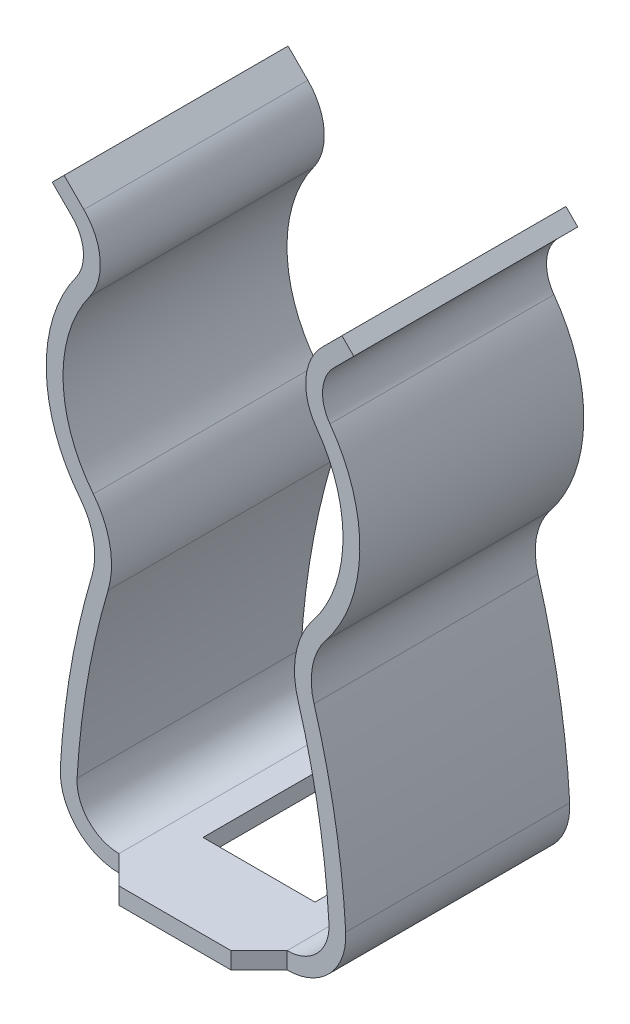
SolidWorks part; units mm, degrees
material "Медь"
ref_plane "Спереди" through (0, 0, 0) normal (0, 0, 1) x (1, 0, 0)
ref_plane "Сверху" through (0, 0, 0) normal (0, 1, 0) x (1, 0, 0)
ref_plane "Справа" through (0, 0, 0) normal (1, 0, 0) x (0, 0, -1)
sketch "Эскиз1" plane through (0, 0, 0) normal (0, 0, 1) x (1, 0, 0)
  line L0 (11.7288, 0) -> (0, 0) construction
  line L2 (0, 12.9831) -> (0, 6.8861) construction
  line L6 (-3.1336, 4.4) -> (3.1336, 4.4) construction
  line L7 (0, 4.4) -> (0, 6.8861) construction
  line L9 (-1.5, 0) -> (0, 0)
  line L10 (0, 0) -> (0, 4.4) construction
  line L13 (-2.1273, 9.6464) -> (-2.4809, 10)
  arc A0 (-2.0246, 8.3527) -> (-1.9585, 5.3323) centre (0, 6.8861) ccw
  arc A2 (-2.0246, 8.3527) -> (-2.1273, 9.6464) centre (-2.8344, 8.9393) ccw
  arc A3 (-1.6953, 3.9742) -> (-1.9585, 5.3323) centre (-3.1336, 4.4) ccw
  arc A6 (-1.6953, 3.9742) -> (-2.2488, 0.7925) centre (11.7288, 0) ccw
  arc A7 (-1.5, 0) -> (-2.2488, 0.7925) centre (-1.5, 0.75) cw
  circle A20 centre (0, 6.8861) radius 2.5 construction
  point P1 (0, 0)
  dimension "D6" = 0.75
  dimension "D8" = 10
  dimension "D9" = 4.4
  dimension "D10" = 5
  dimension "D2" = 2.5
  dimension "D3" = 1
  dimension "D4" = 14
  dimension "D7" = 1.5
  dimension "D5" = 1.5
  dimension "D11" = 45
  dimension "D12" = 0.5
extrude "Вытянуть-Тонкостенный1" add sketch "Эскиз1" along normal mid plane 4 thin thin type one direction reverse wall 0.3
mirror "Зеркальное отражение1" about plane through (0, 0, 0) normal (1, 0, 0) of "Вытянуть-Тонкостенный1"
sketch "Эскиз2" plane through (0, -0.3, 0) normal (0, -1, 0) x (1, 0, 0)
  line L0 (-1.5, 2) -> (-1, 2.5)
  line L1 (-1, 2.5) -> (1, 2.5)
  line L2 (1, 2.5) -> (1.5, 2)
  line L3 (1.5, 2) -> (-1.5, 2)
  line L4 (-1.5, -2) -> (-1, -2.5)
  line L5 (-1, -2.5) -> (1, -2.5)
  line L6 (1, -2.5) -> (1.5, -2)
  line L7 (1.5, -2) -> (-1.5, -2)
  dimension "D1" = 0.5
  dimension "D2" = 0.5
  dimension "D3" = 135
  dimension "D4" = 135
extrude "Бобышка-Вытянуть1" add sketch "Эскиз2" against normal up to surface (0.3 mm away)
sketch "Эскиз3" plane through (0, -0.3, 0) normal (0, -1, 0) x (1, 0, 0)
  line L1 (-1, -1) -> (1, -1)
  line L2 (-1, -1) -> (-1, 1)
  line L3 (-1, 1) -> (1, 1)
  line L4 (1, -1) -> (1, 1)
  line L5 (0, 1) -> (0, -1) construction
  line L6 (-1, 0) -> (1, 0) construction
  point P0 (0, 0)
  dimension "D1" = 2
extrude "Вырез-Вытянуть1" cut sketch "Эскиз3" against normal up to next
ref_axis "Fuse_holder_axes" through (0, 13.593, 0) along (0, -1, 0)
